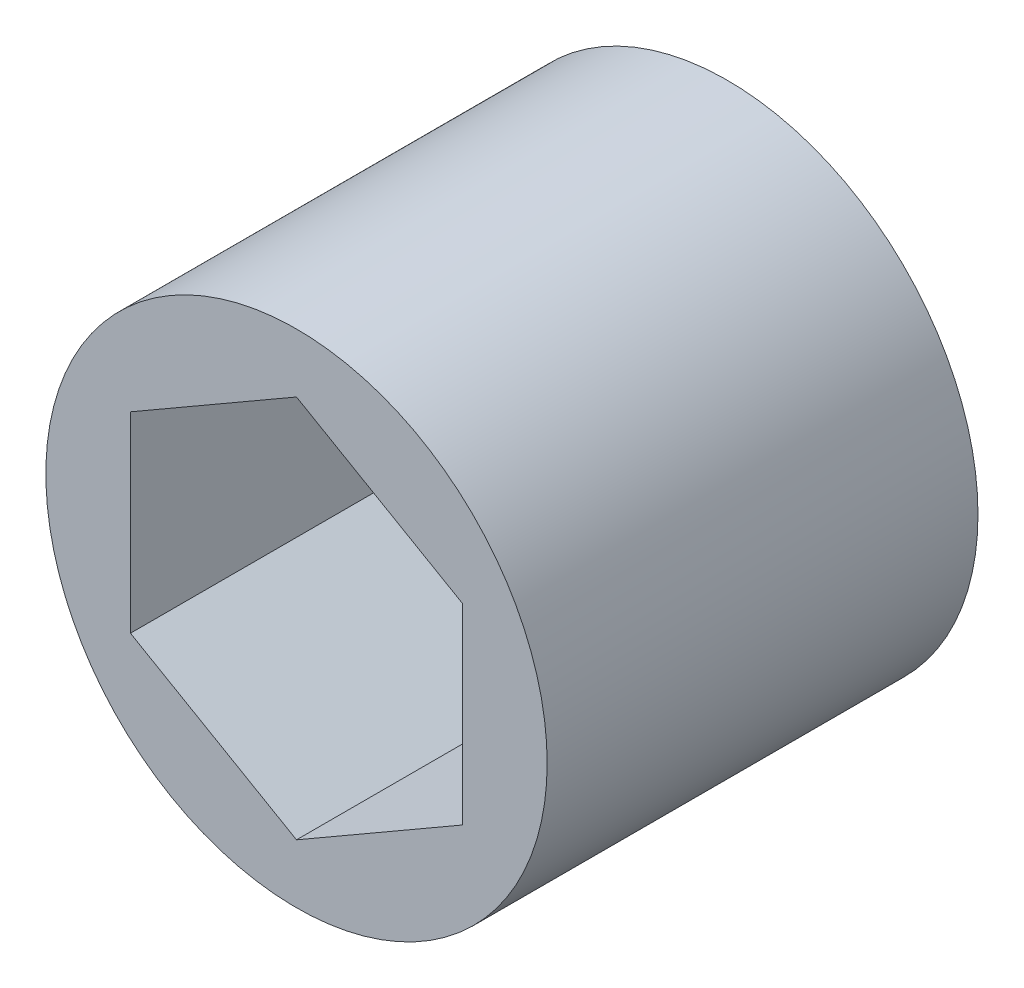
SolidWorks part; units mm, degrees
material "Nylon 101"
ref_plane "Front Plane" through (0, 0, 0) normal (0, 0, 1) x (1, 0, 0)
ref_plane "Top Plane" through (0, 0, 0) normal (0, 1, 0) x (1, 0, 0)
ref_plane "Right Plane" through (0, 0, 0) normal (1, 0, 0) x (0, 0, -1)
sketch "Sketch1" plane through (0, 0, 0) normal (0, 0, 1) x (1, 0, 0)
  line L1 (0, 7.7723) -> (-6.731, 3.8861)
  line L2 (-6.731, 3.8861) -> (-6.731, -3.8861)
  line L3 (-6.731, -3.8861) -> (0, -7.7723)
  line L4 (0, -7.7723) -> (6.731, -3.8861)
  line L5 (6.731, -3.8861) -> (6.731, 3.8861)
  line L6 (6.731, 3.8861) -> (0, 7.7723)
  circle A0 centre (0, 0) radius 10.16
  circle A1 centre (0, 0) radius 6.731 construction
  point P3 (0, 0)
  dimension "D1" = 20.32
  dimension "D2" = 13.462
extrude "Boss-Extrude1" add sketch "Sketch1" along normal mid plane 17.4625
